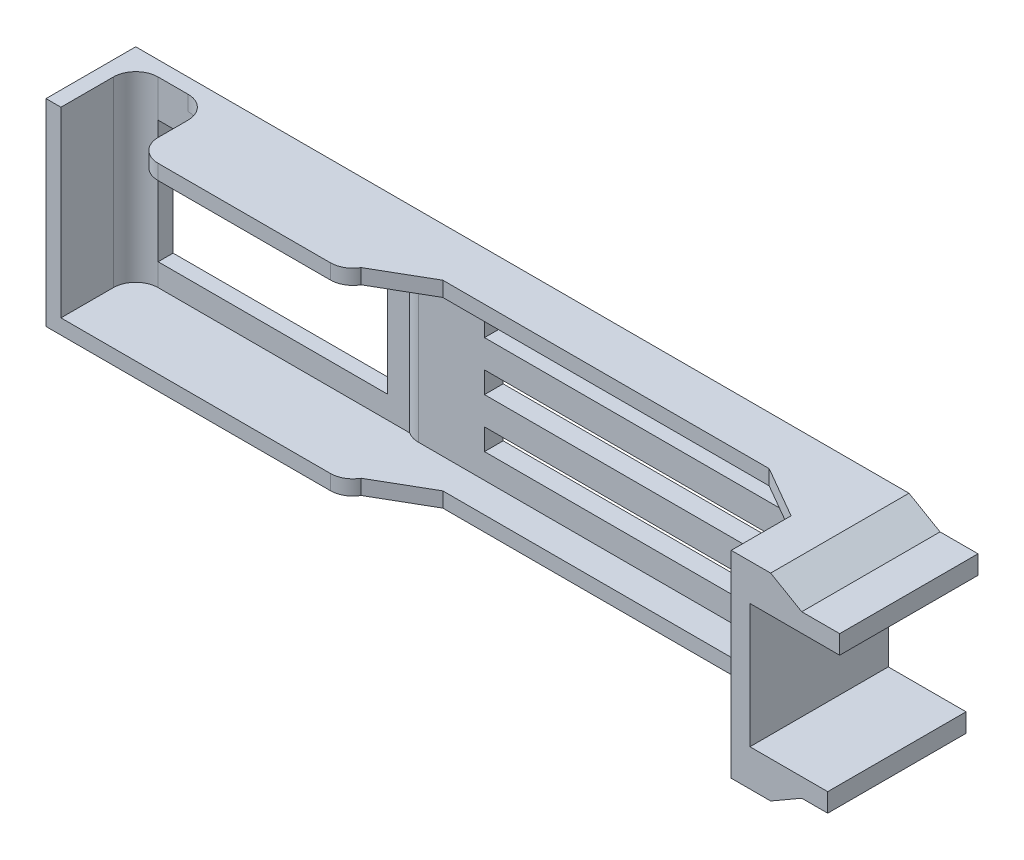
SolidWorks part; units mm, degrees
ref_plane "Plan de face" through (0, 0, 0) normal (0, 0, 1) x (1, 0, 0)
ref_plane "Plan de dessus" through (0, 0, 0) normal (0, 1, 0) x (1, 0, 0)
ref_plane "Plan de droite" through (0, 0, 0) normal (1, 0, 0) x (0, 0, -1)
sketch "Esquisse1" plane through (0, 0, 0) normal (0, 0, 1) x (1, 0, 0)
  line L1 (0, 0) -> (20.32, 0)
  line L2 (0, 0) -> (0, 13.2)
  line L3 (0, 13.2) -> (20.32, 13.2)
  line L4 (20.32, 0) -> (20.32, 13.2)
  dimension "D1" = 20.32
  dimension "D2" = 13.2
extrude "Boss.-Extru.1" add sketch "Esquisse1" along normal blind 6
sketch "Esquisse2" plane through (0, 0, 6) normal (0, 0, 1) x (1, 0, 0)
  line L0 (0, 13.2) -> (0, 0) construction
  line L1 (1, 1) -> (19.32, 1)
  line L2 (1, 1) -> (1, 12.2)
  line L3 (1, 12.2) -> (19.32, 12.2)
  line L4 (19.32, 1) -> (19.32, 12.2)
  line L5 (0, 0) -> (20.32, 0) construction
  line L6 (20.32, 13.2) -> (0, 13.2) construction
  line L7 (20.32, 0) -> (20.32, 13.2) construction
  dimension "D1" = 1
  dimension "D2" = 1
  dimension "D3" = 1
  dimension "D4" = 1
extrude "Enlèv. mat.-Extru.1" cut sketch "Esquisse2" against normal blind 5
sketch "Esquisse3" plane through (0, 0, 6) normal (0, 0, 1) x (1, 0, 0)
  line L0 (1, 12.2) -> (1, 1) construction
  line L1 (1, 12.2) -> (6, 12.2)
  line L2 (1, 12.2) -> (1, 13.2)
  line L3 (1, 13.2) -> (6, 13.2)
  line L4 (6, 12.2) -> (6, 13.2)
  line L5 (19.32, 12.2) -> (1, 12.2) construction
  line L6 (20.32, 13.2) -> (0, 13.2) construction
  dimension "D1" = 0
  dimension "D2" = 0
  dimension "D3" = 0
  dimension "D4" = 5
extrude "Enlèv. mat.-Extru.2" cut sketch "Esquisse3" against normal blind 5
sketch "Esquisse4" plane through (0, 0, 1) normal (0, 0, 1) x (1, 0, 0)
  line L0 (1, 13.2) -> (1, 1) construction
  line L1 (2.5, 10.7) -> (17.82, 10.7)
  line L2 (2.5, 10.7) -> (2.5, 2.5)
  line L3 (2.5, 2.5) -> (17.82, 2.5)
  line L4 (17.82, 10.7) -> (17.82, 2.5)
  line L5 (1, 1) -> (19.32, 1) construction
  line L6 (19.32, 1) -> (19.32, 12.2) construction
  line L7 (19.32, 12.2) -> (6, 12.2) construction
  dimension "D1" = 1.5
  dimension "D2" = 1.5
  dimension "D3" = 1.5
  dimension "D4" = 1.5
extrude "Enlèv. mat.-Extru.3" cut sketch "Esquisse4" against normal through all
sketch "Esquisse6" plane through (0, 0, 6) normal (0, 0, 1) x (1, 0, 0)
  line L0 (19.32, 12.2) -> (6, 12.2) construction
  line L1 (19.32, 12.2) -> (20.32, 12.2)
  line L2 (19.32, 12.2) -> (19.32, 1)
  line L3 (19.32, 1) -> (20.32, 1)
  line L4 (20.32, 12.2) -> (20.32, 1)
  line L5 (1, 1) -> (19.32, 1) construction
  line L6 (19.32, 1) -> (19.32, 12.2) construction
  line L7 (20.32, 0) -> (20.32, 13.2) construction
  dimension "D1" = 0
  dimension "D2" = 0
  dimension "D3" = 0
  dimension "D4" = 0
extrude "Enlèv. mat.-Extru.4" cut sketch "Esquisse6" against normal blind 4.75
sketch "Esquisse7" plane through (0, 0, 0) normal (0, 0, -1) x (-1, 0, 0)
  line L0 (-20.32, 0) -> (-20.32, 13.2) construction
  line L1 (-20.32, 13.2) -> (-50.32, 13.2)
  line L2 (-20.32, 13.2) -> (-20.32, 0)
  line L3 (-20.32, 0) -> (-50.32, 0)
  line L4 (-50.32, 13.2) -> (-50.32, 0)
  line L5 (-20.32, 13.2) -> (0, 13.2) construction
  line L6 (0, 0) -> (-20.32, 0) construction
  dimension "D1" = 0
  dimension "D2" = 0
  dimension "D3" = 0
  dimension "D4" = 30
extrude "Boss.-Extru.2" add sketch "Esquisse7" against normal blind 1.25
sketch "Esquisse8" plane through (0, 0, 1.25) normal (0, 0, 1) x (1, 0, 0)
  line L0 (20.32, 13.2) -> (50.32, 13.2) construction
  line L1 (49.07, 13.2) -> (50.32, 13.2)
  line L2 (49.07, 13.2) -> (49.07, 0)
  line L3 (49.07, 0) -> (50.32, 0)
  line L4 (50.32, 13.2) -> (50.32, 0)
  line L5 (50.32, 13.2) -> (50.32, 0) construction
  line L6 (50.32, 0) -> (20.32, 0) construction
  dimension "D1" = 0
  dimension "D2" = 0
  dimension "D3" = 1.25
  dimension "D4" = 0
extrude "Boss.-Extru.3" add sketch "Esquisse8" along normal blind 8
sketch "Esquisse9" plane through (50.32, 0, 0) normal (1, 0, 0) x (0, 0, -1)
  line L1 (-9.25, 12) -> (0, 12)
  line L2 (-9.25, 12) -> (-9.25, 10.75)
  line L3 (-9.25, 10.75) -> (0, 10.75)
  line L4 (0, 12) -> (0, 10.75)
  line L5 (-9.25, 0) -> (-9.25, 13.2) construction
  line L6 (0, 13.2) -> (0, 0) construction
  line L7 (-9.25, 0) -> (0, 0) construction
  line L8 (-9.25, 2.45) -> (0, 2.45)
  line L9 (-9.25, 2.45) -> (-9.25, 1.2)
  line L10 (-9.25, 1.2) -> (0, 1.2)
  line L11 (0, 2.45) -> (0, 1.2)
  line L12 (-9.25, 13.2) -> (0, 13.2) construction
  dimension "D1" = 1.2
  dimension "D2" = 0
  dimension "D3" = 0
  dimension "D4" = 1.25
  dimension "D5" = 1.2
  dimension "D6" = 0
  dimension "D7" = 0
  dimension "D8" = 1.25
  dimension "D9" = 8.3
extrude "Boss.-Extru.4" add sketch "Esquisse9" along normal blind 6
chamfer "Chanfrein1" distance 2 angle 60 2 edges at (50.32, 1.2, 4.625) (50.32, 12, 4.625) first distance on face at (50.32, 0.6, 4.625) first distance on face at (50.32, 12.6, 4.625)
sketch "Esquisse10" plane through (0, 0, 1.25) normal (0, 0, 1) x (1, 0, 0)
  line L0 (20.32, 12.2) -> (20.32, 13.2) construction
  line L1 (20.32, 13.2) -> (49.07, 13.2)
  line L2 (20.32, 13.2) -> (20.32, 12.2)
  line L3 (20.32, 12.2) -> (49.07, 12.2)
  line L4 (49.07, 13.2) -> (49.07, 12.2)
  line L5 (49.07, 13.2) -> (49.07, 0) construction
  line L6 (20.32, 13.2) -> (6, 13.2) construction
  line L7 (20.32, 1) -> (49.07, 1)
  line L8 (20.32, 1) -> (20.32, 0)
  line L9 (20.32, 0) -> (49.07, 0)
  line L10 (49.07, 1) -> (49.07, 0)
  line L11 (49.07, 0) -> (20.32, 0) construction
  line L12 (20.32, 0) -> (20.32, 1) construction
  dimension "D1" = 1
  dimension "D2" = 0
  dimension "D3" = 0
  dimension "D4" = 0
  dimension "D5" = 0
  dimension "D6" = 0
  dimension "D7" = 0
extrude "Boss.-Extru.5" add sketch "Esquisse10" along normal blind 2
chamfer "Chanfrein2" distance 2 angle 60 4 edges at (49.07, 0.5, 3.25) (49.07, 12.7, 3.25) (20.32, 0.5, 3.25) (20.32, 12.7, 3.25) first distance on face at (49.07, 6.6, 4.25) first distance on face at (20.32, 0.5, 4.625) first distance on face at (20.32, 12.7, 4.625)
sketch "Esquisse11" plane through (0, 0, 1.25) normal (0, 0, 1) x (1, 0, 0)
  line L0 (49.07, 12.2) -> (19.32, 12.2) construction
  line L1 (24.57, 10.7) -> (45.57, 10.7)
  line L2 (24.57, 10.7) -> (24.57, 9.2665)
  line L3 (24.57, 9.2665) -> (45.57, 9.2665)
  line L4 (45.57, 10.7) -> (45.57, 9.2665)
  line L5 (49.07, 12.2) -> (49.07, 1) construction
  line L6 (24.57, 7.4) -> (24.57, 5.9665)
  line L7 (24.57, 7.4) -> (45.57, 7.4)
  line L8 (45.57, 7.4) -> (45.57, 5.9665)
  line L9 (24.57, 5.9665) -> (45.57, 5.9665)
  line L10 (24.57, 4.1) -> (24.57, 2.6665)
  line L11 (24.57, 4.1) -> (45.57, 4.1)
  line L12 (45.57, 4.1) -> (45.57, 2.6665)
  line L13 (24.57, 2.6665) -> (45.57, 2.6665)
  dimension "D1" = 1.5
  dimension "D2" = 21
  dimension "D3" = 3.5
  dimension "D4" = 3
extrude "Enlèv. mat.-Extru.5" cut sketch "Esquisse11" against normal blind 2
sketch "Esquisse12" plane through (0, 1.2, 0) normal (0, -1, 0) x (-1, 0, 0)
  line L0 (-56.32, -9.25) -> (-56.32, 0) construction
  line L1 (-55.52, -9.25) -> (-56.32, -9.25)
  line L2 (-55.52, -9.25) -> (-55.52, 0)
  line L3 (-55.52, 0) -> (-56.32, 0)
  line L4 (-56.32, -9.25) -> (-56.32, 0)
  line L5 (-56.32, -9.25) -> (-53.7841, -9.25) construction
  line L6 (-56.32, 0) -> (-53.7841, 0) construction
  point P4 (-55.7685, -1.5266)
  dimension "D1" = 0
  dimension "D2" = 0
  dimension "D3" = 0
  dimension "D4" = 0.8
extrude "Enlèv. mat.-Extru.6" cut sketch "Esquisse12" against normal blind 2
fillet "Congé1" radius 1.5 6 edges at (20.32, 0.5, 6) (20.32, 12.7, 6) (1, 7.1, 1) (6, 12.7, 1) (19.32, 6.6, 1.25) (6, 12.7, 6)
